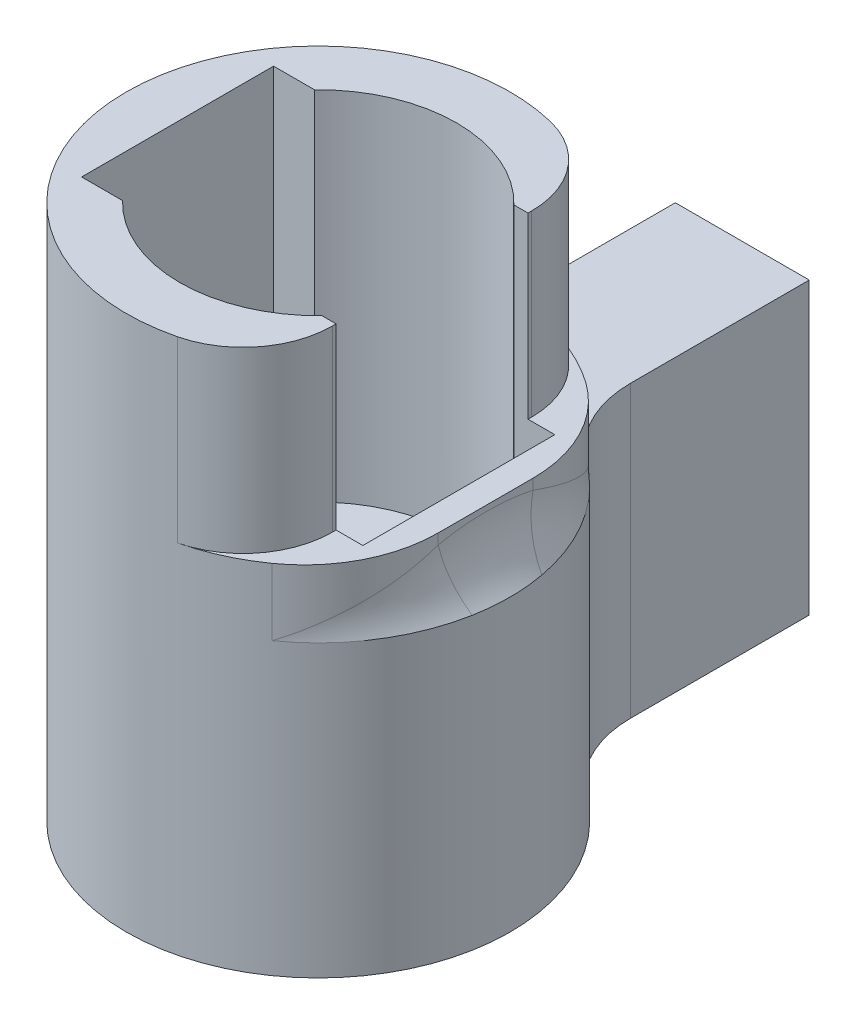
SolidWorks part; units mm, degrees
ref_plane "Спереди" through (0, 0, 0) normal (0, 0, 1) x (1, 0, 0)
ref_plane "Сверху" through (0, 0, 0) normal (0, 1, 0) x (1, 0, 0)
ref_plane "Справа" through (0, 0, 0) normal (1, 0, 0) x (0, 0, -1)
sketch "Sketch1" plane through (0, 0, 0) normal (0, 1, 0) x (1, 0, 0)
  circle A0 centre (0, 0) radius 4.3
  circle A1 centre (0, 0) radius 1.6
  dimension "D1" = 8.6
  dimension "D2" = 3.2
extrude "Boss-Extrude1" add sketch "Sketch1" along normal blind 12
sketch "Sketch2" plane through (0, 12, 0) normal (0, 1, 0) x (1, 0, 0)
  circle A0 centre (0, 0) radius 3.1
  dimension "D1" = 6.2
extrude "Cut-Extrude1" cut sketch "Sketch2" against normal blind 8
sketch "Sketch3" plane through (0, 12, 0) normal (0, 1, 0) x (1, 0, 0)
  line L1 (3.15, -2.15) -> (-3.15, -2.15)
  line L2 (3.15, -2.15) -> (3.15, 2.15)
  line L3 (3.15, 2.15) -> (-3.15, 2.15)
  line L4 (-3.15, -2.15) -> (-3.15, 2.15)
  line L5 (3.15, -2.15) -> (-3.15, 2.15) construction
  line L6 (3.15, 2.15) -> (-3.15, -2.15) construction
  point P0 (0, 0)
  dimension "D1" = 4.3
  dimension "D2" = 6.3
extrude "Cut-Extrude2" cut sketch "Sketch3" against normal blind 6
sketch "Sketch6" plane through (0, 0, 0) normal (0, -1, 0) x (1, 0, 0)
  line L0 (-4.3, 0) -> (4.3, 0) construction
  line L1 (0, 0) -> (0, 10) construction
  line L2 (0, 0) -> (0, -10) construction
  line L3 (1.5, 9.5) -> (-1.5, 9.5) construction
  line L4 (1.5, 9.5) -> (1.5, 3.5) construction
  line L5 (1.5, 3.5) -> (-1.5, 3.5) construction
  line L6 (-1.5, 9.5) -> (-1.5, 3.5) construction
  line L7 (1.5, 9.5) -> (-1.5, 3.5) construction
  line L8 (1.5, 3.5) -> (-1.5, 9.5) construction
  line L10 (1.5, -9.5) -> (-1.5, -9.5)
  line L11 (1.5, -9.5) -> (1.5, -3.5)
  line L12 (1.5, -3.5) -> (-1.5, -3.5)
  line L13 (-1.5, -9.5) -> (-1.5, -3.5)
  line L14 (1.5, -9.5) -> (-1.5, -3.5) construction
  line L15 (1.5, -3.5) -> (-1.5, -9.5) construction
  circle A0 centre (0, 0) radius 4.3 construction
  point P8 (0, 6.5)
  point P13 (0, -6.5)
  dimension "D1" = 10
  dimension "D2" = 3.5
  dimension "D3" = 6
  dimension "D4" = 3
  dimension "D5" = 3.5
extrude "Boss-Extrude3" add sketch "Sketch6" against normal blind 6.5
sketch "Sketch7" plane through (0, 12, 0) normal (0, 1, 0) x (1, 0, 0)
  line L0 (-3.75, 2.1042) -> (-3.75, -2.1042) construction
  line L1 (3.75, 2.1042) -> (3.75, -2.1042) construction
  line L2 (-3.15, 2.15) -> (-3.15, -2.15) construction
  line L4 (3.75, 2.1042) -> (3.75, -2.1042)
  circle A0 centre (0, 0) radius 4.3 construction
  arc A2 (3.75, 2.1042) -> (3.75, -2.1042) centre (0.1236, 0) cw
  dimension "D1" = 7.5
extrude "Cut-Extrude4" cut sketch "Sketch7" against normal blind 5.5
fillet "Fillet1" radius 3 2 edges at (3.75, 9.25, 2.1042) (3.75, 9.25, -2.1042)
fillet "Fillet2" radius 2 3 edges at (3.4139, 6.5, -2.4416) (3.4139, 6.5, 2.4416) (3.75, 6.5, 0)
sketch "Sketch9" plane through (0, 12, 0) normal (0, 1, 0) x (1, 0, 0)
  line L0 (2.55, 3.4618) -> (2.55, -3.4618)
  line L2 (3.75, 1.0618) -> (3.75, -1.0618)
  arc A0 (3.75, 1.0618) -> (2.4808, 3.5122) centre (0.75, 1.0618) ccw construction
  arc A1 (2.4808, -3.5122) -> (3.75, -1.0618) centre (0.75, -1.0618) ccw construction
  arc A2 (3.75, 1.0618) -> (2.55, 3.4618) centre (0.75, 1.0618) ccw
  arc A3 (3.75, -1.0618) -> (2.55, -3.4618) centre (0.75, -1.0618) cw
  dimension "D1" = 1.2
extrude "Cut-Extrude6" cut sketch "Sketch9" against normal blind 4
fillet "Fillet4" radius 2.5 2 edges at (1.5, 3.25, -4.0299) (-1.5, 3.25, -4.0299)
fillet "Fillet5" radius 2 2 edges at (2.55, 10, -3.4618) (2.55, 10, 3.4618)
